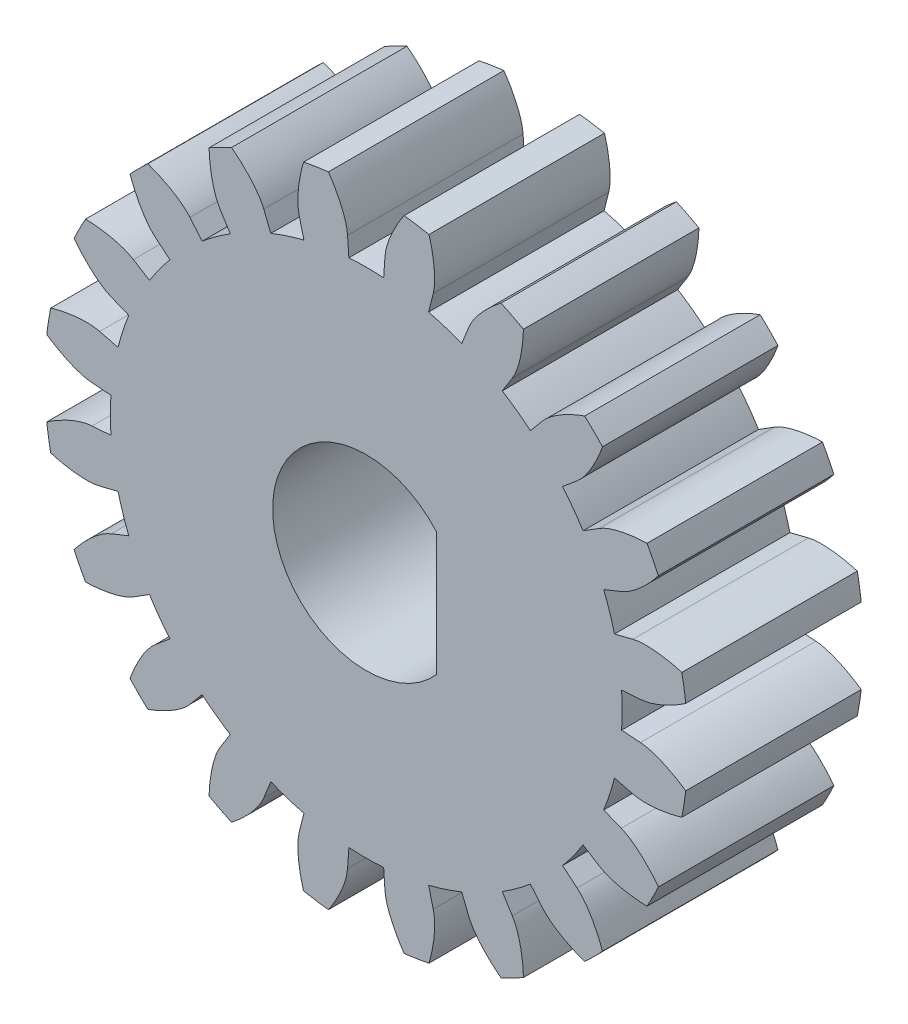
SolidWorks part; units mm, degrees
ref_plane "前视基准面" through (0, 0, 0) normal (0, 0, 1) x (1, 0, 0)
ref_plane "上视基准面" through (0, 0, 0) normal (0, 1, 0) x (1, 0, 0)
ref_plane "右视基准面" through (0, 0, 0) normal (1, 0, 0) x (0, 0, -1)
other "Configuration Table"
sketch "草图1" plane through (0, 0, 0) normal (0, 0, 1) x (1, 0, 0)
  line L0 (0, 0) -> (5, 0) construction
  line L1 (0, 0) -> (4.9846, 0.3923) construction
  line L2 (0, 0) -> (4.6876, 0.3194)
  line L3 (4.9846, 0.3923) -> (4.9846, -0.3923) construction
  line L4 (0, 0) -> (4.6876, -0.3194)
  circle A0 centre (0, 0) radius 5.5
  circle A1 centre (0, 0) radius 5 construction
  circle A2 centre (0, 0) radius 4.375
  circle A3 centre (0, 0) radius 4.6985 construction
  circle A4 centre (0, 0) radius 1.6
  spline S0 degree 4 poles (4.6876, 0.3194) (4.7233, 0.3218) (4.8225, 0.336) (5.0062, 0.3926) (5.2885, 0.5242) (5.6241, 0.7499) (6.0094, 1.0976) (6.395, 1.5688) (6.7398, 2.1414) (7.0933, 2.9696) (7.3065, 3.8467) (7.3947, 4.7795) (7.347, 5.8934) (7.1568, 6.9938) (6.7515, 8.227) (6.0949, 9.5107) (5.2611, 10.6861) (4.2765, 11.7378) (3.1662, 12.6551) (1.9531, 13.4307) (0.6586, 14.0604) (-0.5283, 14.4821) (-1.4854, 14.7287) (-2.1912, 14.8654) (-2.6338, 14.9356) (-2.9917, 14.9827) (-3.3451, 15.0208) (-3.7095, 15.05) (-4.0266, 15.0684) (-4.3306, 15.0786) (-4.6986, 15.0842) (-4.9527, 15.0816) (-5.4001, 15.0704) (-5.6957, 15.0494) (-6.0237, 15.027) (-6.2862, 14.9991) (-6.5922, 14.9657) (-6.7961, 14.9366) (-6.9439, 14.9154) (-7.0152, 14.9043) knots 0 0 0 0 0 0.005604 0.015718 0.02996 0.048734 0.068727 0.096889 0.125051 0.153212 0.209535 0.237696 0.271429 0.327752 0.384075 0.440398 0.496721 0.553044 0.609367 0.66569 0.722013 0.778336 0.806497 0.820578 0.834659 0.84874 0.86282 0.876901 0.890982 0.900036 0.909091 0.931818 0.943182 0.954545 0.965909 0.977273 0.988636 1 1 1 1 1 construction
  spline S1 degree 4 poles (4.6876, 0.3194) (4.7233, 0.3218) (4.8225, 0.336) (5.0062, 0.3926) (5.2885, 0.5242) (5.6241, 0.7499) (6.0094, 1.0976) (6.395, 1.5688) (6.7398, 2.1414) (7.0933, 2.9696) (7.3065, 3.8467) (7.3947, 4.7795) (7.347, 5.8934) (7.1568, 6.9938) (6.7515, 8.227) (6.0949, 9.5107) (5.2611, 10.6861) (4.2765, 11.7378) (3.1662, 12.6551) (1.9531, 13.4307) (0.6586, 14.0604) (-0.5283, 14.4821) (-1.4854, 14.7287) (-2.1912, 14.8654) (-2.6338, 14.9356) (-2.9917, 14.9827) (-3.3451, 15.0208) (-3.7095, 15.05) (-4.0266, 15.0684) (-4.3306, 15.0786) (-4.5463, 15.0819) (-4.6529, 15.0825) (-4.7054, 15.0825) knots 0 0 0 0 0 0.005604 0.015718 0.02996 0.048734 0.068727 0.096889 0.125051 0.153212 0.209535 0.237696 0.271429 0.327752 0.384075 0.440398 0.496721 0.553044 0.609367 0.66569 0.722013 0.778336 0.806497 0.820578 0.834659 0.84874 0.86282 0.876901 0.890982 0.900036 0.909091 0.909091 0.909091 0.909091 0.909091
  spline S2 degree 4 poles (4.6876, -0.3194) (4.7233, -0.3218) (4.8225, -0.336) (5.0062, -0.3926) (5.2885, -0.5242) (5.6241, -0.7499) (6.0094, -1.0976) (6.395, -1.5688) (6.7398, -2.1414) (7.0933, -2.9696) (7.3065, -3.8467) (7.3947, -4.7795) (7.347, -5.8934) (7.1568, -6.9938) (6.7515, -8.227) (6.0949, -9.5107) (5.2611, -10.6861) (4.2765, -11.7378) (3.1662, -12.6551) (1.9531, -13.4307) (0.6586, -14.0604) (-0.5283, -14.4821) (-1.4854, -14.7287) (-2.1912, -14.8654) (-2.6338, -14.9356) (-2.9917, -14.9827) (-3.3451, -15.0208) (-3.7095, -15.05) (-4.0266, -15.0684) (-4.3306, -15.0786) (-4.6986, -15.0842) (-4.9527, -15.0816) (-5.4001, -15.0704) (-5.6957, -15.0494) (-6.0237, -15.027) (-6.2862, -14.9991) (-6.5922, -14.9657) (-6.7961, -14.9366) (-6.9439, -14.9154) (-7.0152, -14.9043) knots 0 0 0 0 0 0.005604 0.015718 0.02996 0.048734 0.068727 0.096889 0.125051 0.153212 0.209535 0.237696 0.271429 0.327752 0.384075 0.440398 0.496721 0.553044 0.609367 0.66569 0.722013 0.778336 0.806497 0.820578 0.834659 0.84874 0.86282 0.876901 0.890982 0.900036 0.909091 0.931818 0.943182 0.954545 0.965909 0.977273 0.988636 1 1 1 1 1 construction
  spline S3 degree 4 poles (4.6876, -0.3194) (4.7233, -0.3218) (4.8225, -0.336) (5.0062, -0.3926) (5.2885, -0.5242) (5.6241, -0.7499) (6.0094, -1.0976) (6.395, -1.5688) (6.7398, -2.1414) (7.0933, -2.9696) (7.3065, -3.8467) (7.3947, -4.7795) (7.347, -5.8934) (7.1568, -6.9938) (6.7515, -8.227) (6.0949, -9.5107) (5.2611, -10.6861) (4.2765, -11.7378) (3.1662, -12.6551) (1.9531, -13.4307) (0.6586, -14.0604) (-0.5283, -14.4821) (-1.4854, -14.7287) (-2.1912, -14.8654) (-2.6338, -14.9356) (-2.9917, -14.9827) (-3.3451, -15.0208) (-3.7095, -15.05) (-4.0266, -15.0684) (-4.3306, -15.0786) (-4.5463, -15.0819) (-4.6529, -15.0825) (-4.7054, -15.0825) knots 0 0 0 0 0 0.005604 0.015718 0.02996 0.048734 0.068727 0.096889 0.125051 0.153212 0.209535 0.237696 0.271429 0.327752 0.384075 0.440398 0.496721 0.553044 0.609367 0.66569 0.722013 0.778336 0.806497 0.820578 0.834659 0.84874 0.86282 0.876901 0.890982 0.900036 0.909091 0.909091 0.909091 0.909091 0.909091
  point P15 (4.9846, 0)
  dimension "齿顶圆直径" = 11
  dimension "分度圆直径" = 10
  dimension "齿根圆直径" = 8.75
  dimension "基圆直径" = 9.3969
  dimension "内孔直径" = 3.2
  dimension "渐近线镜像线夹角" = 4.5
extrude "凸台-拉伸1" add sketch "草图1" along normal blind 3 contours A0 | A4
extrude "切除-拉伸1" cut sketch "草图1<3>" along normal through all contours A2 S3 A0 S1 region at (5.0102, 0, 0)
sketch "草图1<3>" plane through (0, 0, 0) normal (0, 0, 1) x (1, 0, 0) same geometry as "草图1"
pattern_circular "阵列(圆周)1" count 20 every 18 about axis through (0, 0, 3) along (0, 0, 1) of "切除-拉伸1"
sketch "草图2" plane through (0, 0, 0) normal (0, 0, -1) x (-1, 0, 0)
  line L1 (-1.2, 1.0583) -> (-1.2, -1.0583)
  circle A1 centre (0, 0) radius 1.6 construction
  circle A2 centre (0, 0) radius 1.6
  dimension "D1" = 1.2
extrude "凸台-拉伸2" add sketch "草图2" against normal through all contours L1 A2 region at (1.3618, 0, 0)
equation "\"m\"= 0.5'模数"
equation "\"z\"= 20'齿数"
equation "\"a\"= 20度'压力角"
equation "\"d\"= \"m\" * \"z\"'分度圆直径"
equation "\"da\"= ( \"z\" + 2 ) * \"m\"'齿顶圆直径"
equation "\"df\"= ( \"z\" - 2.5 ) * \"m\"'齿根圆直径"
equation "\"s\"= 0.5 * PI * \"m\"'分度圆齿厚"
equation "\"r\"= 0.38 * \"m\"'齿根圆角"
equation "\"B\"= 0.3 * \"d\"'齿厚"
equation "\"db\"= \"m\" * \"z\" * cos ( \"a\" )'基圆直径"
equation "\"rb\"= \"db\" / 2'基圆半径"
equation "\"齿顶圆直径@草图1\"= \"da\""
equation "\"分度圆直径@草图1\"= \"d\""
equation "\"齿根圆直径@草图1\"= \"df\""
equation "\"基圆直径@草图1\"= \"db\""
equation "\"渐近线镜像线夹角@草图1\"= 360 / 4 / \"z\""
equation "\"h\" = 3'齿轮厚度"
equation "\"ir\"= 3.2'内孔直径"
equation "\"内孔直径@草图1\"= \"ir\""
equation "\"齿轮厚@凸台-拉伸1\"= \"h\""
equation "\"齿轮夹角@阵列(圆周)1\"= 360 / \"z\""
equation "\"齿数@阵列(圆周)1\"= \"z\""
